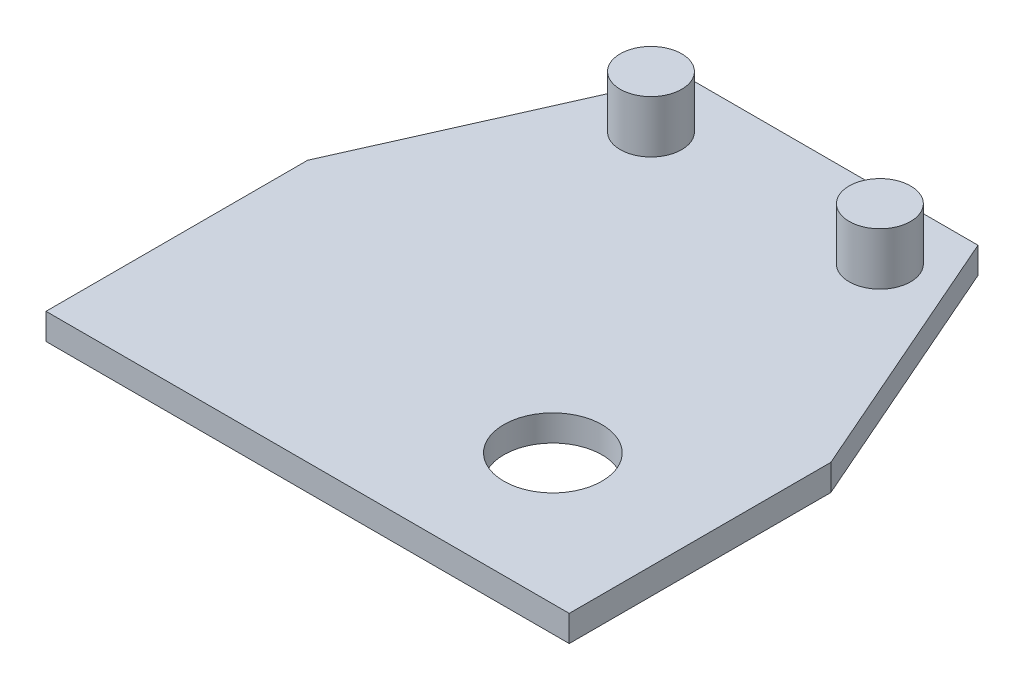
SolidWorks part; units mm, degrees
ref_plane "Front Plane" through (0, 0, 0) normal (0, 0, 1) x (1, 0, 0)
ref_plane "Top Plane" through (0, 0, 0) normal (0, 1, 0) x (1, 0, 0)
ref_plane "Right Plane" through (0, 0, 0) normal (1, 0, 0) x (0, 0, -1)
sketch "Sketch1" plane through (0, 0, 0) normal (0, 1, 0) x (1, 0, 0)
  line L1 (-20, 10) -> (20, 10)
  line L2 (-20, 10) -> (-20, -10)
  line L3 (-20, -10) -> (20, -10)
  line L4 (20, 10) -> (20, -10)
  point P4 (0, 10)
  point P6 (20, 0)
  dimension "D1" = 40
  dimension "D2" = 20
extrude "Boss-Extrude1" add sketch "Sketch1" along normal blind 2
sketch "Sketch2" plane through (0, 2, 0) normal (0, 1, 0) x (1, 0, 0)
  line L0 (-20, 0) -> (-4, 0) construction
  line L1 (-20, 10) -> (-20, -10) construction
  circle A0 centre (-4, 0) radius 2.35
  dimension "D2" = 4.7
  dimension "D1" = 16
sketch "Sketch5" plane through (0, 2, 0) normal (0, 1, 0) x (1, 0, 0)
  line L1 (-20, 10) -> (30, 10)
  line L2 (-20, 10) -> (-20, 30)
  line L3 (-20, 30) -> (30, 30)
  line L4 (30, 10) -> (30, 30)
  dimension "D1" = 20
extrude "Boss-Extrude4" add sketch "Sketch5" against normal blind 2
sketch "Sketch6" plane through (0, 2, 0) normal (0, 1, 0) x (1, 0, 0)
  line L0 (-20, 25) -> (20, 25) construction
  line L1 (-20, 30) -> (-20, -10) construction
  line L2 (20, -10) -> (20, 10) construction
  line L3 (30, 30) -> (-20, 30) construction
  line L4 (0, 30) -> (0, 25) construction
  circle A0 centre (-8.75, 25) radius 2.35
  circle A1 centre (8.75, 25) radius 2.35
  dimension "D2" = 4.7
  dimension "D3" = 4.7
  dimension "D4" = 17.5
  dimension "D1" = 5
  dimension "D5" = 8.75
extrude "Boss-Extrude5" add sketch "Sketch6" along normal blind 4
sketch "Sketch7" plane through (0, 0, 0) normal (0, -1, 0) x (1, 0, 0)
  line L1 (-5.8, -6.3) -> (-1.25, -6.3)
  line L2 (-5.8, -6.3) -> (-5.8, 6.3)
  line L3 (-5.8, 6.3) -> (-1.25, 6.3)
  line L4 (-1.25, -6.3) -> (-1.25, 6.3)
  line L5 (21.75, 6.3) -> (26.3, 6.3)
  line L6 (21.75, 6.3) -> (21.75, -6.2998)
  line L7 (21.75, -6.2998) -> (26.3, -6.2998)
  line L8 (26.3, 6.3) -> (26.3, -6.2998)
sketch "Sketch15" plane through (0, 2, 0) normal (0, 1, 0) x (1, 0, 0)
  line L0 (-20, 0) -> (17.0642, 0) construction
  line L1 (-20, 30) -> (-20, -10) construction
  line L2 (-20, -10) -> (20, -10) construction
  line L3 (0, 30) -> (0, -10) construction
  circle A0 centre (8.75, 0) radius 3.75
  dimension "D2" = 7.5
  dimension "D3" = 8.75
  dimension "D1" = 10
extrude "Cut-Extrude6" cut sketch "Sketch15" against normal blind 6
sketch "Sketch17" plane through (0, 2, 0) normal (0, 1, 0) x (1, 0, 0)
  line L1 (20, 10) -> (30, 10)
  line L2 (20, 10) -> (20, 30)
  line L3 (20, 30) -> (30, 30)
  line L4 (30, 10) -> (30, 30)
extrude "Cut-Extrude8" cut sketch "Sketch17" against normal through all
sketch "Sketch18" plane through (0, 2, 0) normal (0, 1, 0) x (1, 0, 0)
  line L0 (20, 10) -> (-20, 10) construction
  line L1 (20, -10) -> (20, 30) construction
  line L2 (-20, 30) -> (-20, -10) construction
  line L3 (11.25, 30) -> (-11.1, 30) construction
  line L4 (20, 30) -> (-20, 30) construction
  line L5 (-11.1, 30) -> (-20, 10) construction
  line L6 (11.25, 30) -> (20, 10) construction
  line L7 (-11.1, 30) -> (-20, 10)
  line L8 (-20, 10) -> (-20, 30)
  line L9 (-20, 30) -> (-11.1, 30)
  line L10 (20, 10) -> (11.25, 30)
  line L11 (11.25, 30) -> (20, 30)
  line L12 (20, 30) -> (20, 10)
extrude "Cut-Extrude9" cut sketch "Sketch18" against normal blind 2
